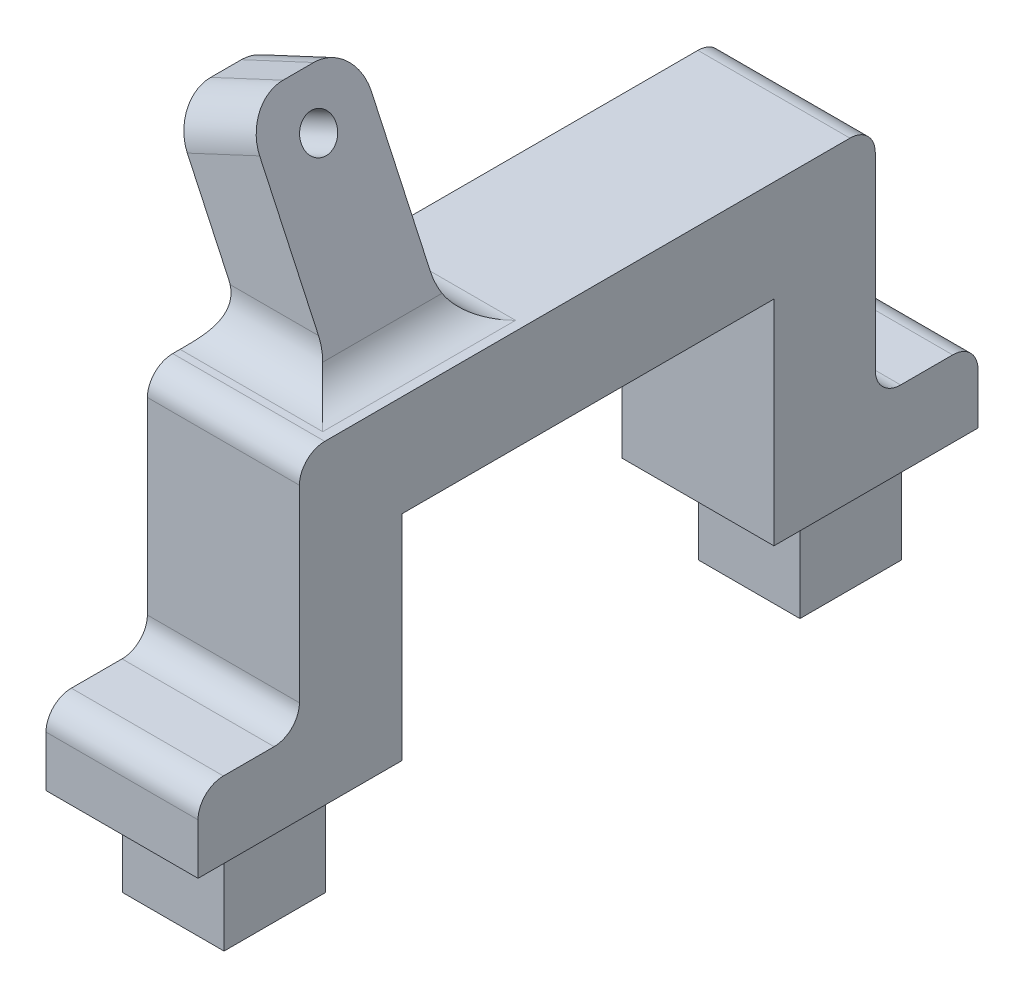
SolidWorks part; units mm, degrees
material "ABS"
ref_plane "Front Plane" through (0, 0, 0) normal (0, 0, 1) x (1, 0, 0)
ref_plane "Top Plane" through (0, 0, 0) normal (0, 1, 0) x (1, 0, 0)
ref_plane "Right Plane" through (0, 0, 0) normal (1, 0, 0) x (0, 0, -1)
sketch "Sketch1" plane through (0, 0, 0) normal (1, 0, 0) x (0, 0, -1)
  line L0 (0, 0) -> (12.7848, 0)
  line L1 (12.7848, 0) -> (12.7848, 13.3902)
  line L2 (12.7848, 13.3902) -> (36.0779, 13.3902)
  line L3 (36.0779, 13.3902) -> (36.0779, 0)
  line L5 (6.351, 19.7402) -> (41.4309, 19.7402)
  line L7 (48.8626, 0) -> (36.0779, 0)
  line L8 (6.351, 19.7402) -> (6.351, 4.7625)
  line L9 (6.351, 4.7625) -> (0, 4.7625)
  line L10 (0, 4.7625) -> (0, 0)
  line L11 (41.4309, 19.7402) -> (42.4279, 19.7402)
  line L12 (42.4279, 19.7402) -> (42.4279, 4.7625)
  line L13 (42.4279, 4.7625) -> (48.8626, 4.7625)
  line L14 (48.8626, 4.7625) -> (48.8626, 0)
  dimension "D1" = 6.35
  dimension "D2" = 12.7848
  dimension "D3" = 12.7848
  dimension "D4" = 0
  dimension "D5" = 13.3902
  dimension "D6" = 23.2931
  dimension "D7" = 35.0799
  dimension "D8" = 6.4338
  dimension "D9" = 4.7625
  dimension "D10" = 4.7625
  dimension "D11" = 6.35
extrude "Boss-Extrude1" add sketch "Sketch1" along normal blind 9.525
ref_plane "Plane2" through (0, 0, -24.4307) normal (0, 0, 1) x (1, 0, 0)
sketch "Sketch2" plane through (0, 4.7625, 0) normal (0, 1, 0) x (1, 0, 0)
  line L0 (0, 48.8626) -> (0, 42.4279) construction
  line L1 (9.525, 48.8626) -> (0, 48.8626) construction
  circle A0 centre (4.7625, 45.6876) radius 0.508
  circle A1 centre (4.7625, 3.1757) radius 0.7938
  dimension "D1" = 4.7625
  dimension "D3" = 42.512
  dimension "D4" = 1.016
  dimension "D2" = 3.175
extrude "Cut-Extrude1" [suppressed] cut sketch "Sketch2" against normal up to next
sketch "Sketch3" plane through (0, 0, 0) normal (-1, 0, 0) x (0, 0, 1)
  line L0 (-36.0779, 0) -> (-48.8626, 0) construction
  line L1 (-36.0779, 13.3902) -> (-36.0779, 0) construction
  circle A0 centre (-38.3232, 6.6853) radius 0.508
  circle A1 centre (-10.5229, 6.6951) radius 0.508
  dimension "D3" = 1.016
  dimension "D1" = 6.6853
  dimension "D2" = 2.2454
  dimension "D4" = 27.8003
extrude "Cut-Extrude2" cut sketch "Sketch3" against normal blind 6.35
fillet "Fillet1" radius 1.5875 6 edges at (4.7625, 4.7625, 0) (4.7625, 4.7625, -6.351) (4.7625, 19.7402, -6.351) (4.7625, 19.7402, -42.4279) (4.7625, 4.7625, -48.8626) (4.7625, 4.7625, -42.4279)
sketch "Esquisse1" plane through (0, 0, 0) normal (0, -1, 0) x (1, 0, 0)
  line L0 (0, -36.0779) -> (0, -48.8626) construction
  line L1 (1.5875, -45.6452) -> (7.9375, -45.6452)
  line L2 (1.5875, -45.6452) -> (1.5875, -39.2952)
  line L3 (1.5875, -39.2952) -> (7.9375, -39.2952)
  line L4 (7.9375, -45.6452) -> (7.9375, -39.2952)
  line L5 (9.525, -48.8626) -> (0, -48.8626) construction
  line L6 (0, -24.4313) -> (9.525, -24.4313) construction
  line L7 (0, -12.7848) -> (0, -36.0779) construction
  line L8 (9.525, -12.7848) -> (9.525, -36.0779) construction
  line L9 (7.9375, -3.2174) -> (7.9375, -9.5674)
  line L10 (1.5875, -9.5674) -> (7.9375, -9.5674)
  line L11 (1.5875, -3.2174) -> (1.5875, -9.5674)
  line L12 (1.5875, -3.2174) -> (7.9375, -3.2174)
  point P6 (0, -42.4702)
  point P7 (1.5875, -42.4702)
  point P10 (4.7625, -48.8626)
  point P11 (4.7625, -45.6452)
  dimension "D1" = 6.35
extrude "Boss.-Extru.1" add sketch "Esquisse1" along normal blind 6.35
ref_plane "Plan1" through (-5.8597, 12.5662, 0) normal (0.4226, -0.9063, 0) x (0, 0, 1)
sketch "Esquisse2" plane through (-5.8597, 12.5662, 0) normal (0.4226, -0.9063, 0) x (0, 0, 1)
  line L0 (-7.9385, -8.3426) -> (-7.9385, -16.9752) construction
  line L1 (-17.9385, -9.9752) -> (-10.9385, -9.9752)
  line L2 (-17.9385, -9.9752) -> (-17.9385, -14.9752)
  line L3 (-17.9385, -14.9752) -> (-10.9385, -14.9752)
  line L4 (-10.9385, -9.9752) -> (-10.9385, -14.9752)
  line L5 (-40.8404, -16.9752) -> (-7.9385, -16.9752) construction
  dimension "D1" = 7
  dimension "D2" = 5
  dimension "D3" = 3
  dimension "D4" = 2
extrude "Boss.-Extru.2" add sketch "Esquisse2" against normal blind 15
sketch "Esquisse3" plane through (9.0406, 4.2157, 0) normal (-0.9063, -0.4226, 0) x (0, 0, 1)
  line L0 (-10.9385, 28.8653) -> (-17.9385, 28.8653) construction
  line L1 (-17.9385, 28.8653) -> (-17.9385, 17.1295) construction
  circle A0 centre (-14.4385, 25.8653) radius 1.1
  dimension "D1" = 2.2
  dimension "D2" = 3
  dimension "D3" = 3.5
extrude "Enlèv. mat.-Extru.1" cut sketch "Esquisse3" against normal through all
fillet "Congé1" radius 2.54 6 edges at (1.8014, 19.7402, -14.4385) (7.3182, 19.7402, -14.4385) (4.5598, 19.7402, -10.9385) (4.5598, 19.7402, -17.9385) (-0.8927, 31.4331, -10.9385) (-0.8927, 31.4331, -17.9385)
